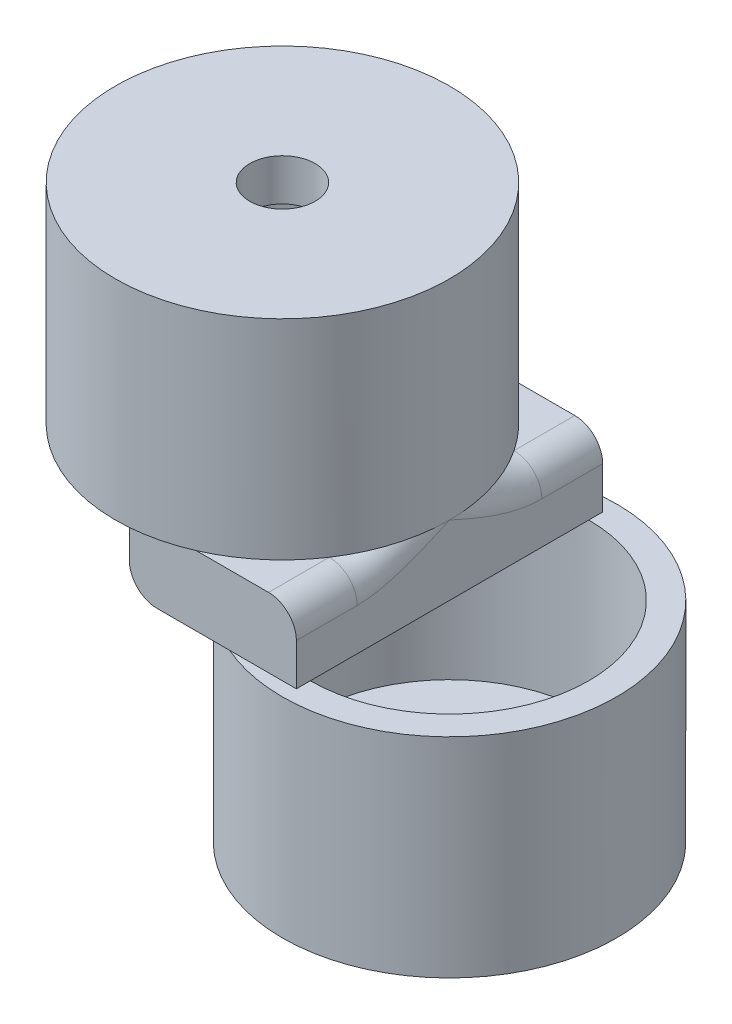
SolidWorks part; units mm, degrees
ref_plane "前视基准面" through (0, 0, 0) normal (0, 0, 1) x (1, 0, 0)
ref_plane "上视基准面" through (0, 0, 0) normal (0, 1, 0) x (1, 0, 0)
ref_plane "右视基准面" through (0, 0, 0) normal (1, 0, 0) x (0, 0, -1)
sketch "草图1" plane through (0, 0, 0) normal (0, 1, 0) x (1, 0, 0)
  circle A0 centre (0, 0) radius 12
  dimension "D1" = 24
extrude "凸台-拉伸1" add sketch "草图1" along normal blind 15
sketch "草图2" plane through (0, 0, 0) normal (0, 1, 0) x (1, 0, 0)
  circle A0 centre (12, 0) radius 12
  circle A1 centre (0, 0) radius 12 construction
  point P5 (9.8465, -1.7455)
  point P6 (9.7679, 2.1422)
  point P7 (9.9986, 0.17)
extrude "凸台-拉伸2" add sketch "草图2" against normal blind 15 from offset 5 offset against normal yes
sketch "草图3" plane through (0, 0, 0) normal (0, 1, 0) x (1, 0, 0)
  circle A2 centre (0, 0) radius 10
  circle A3 centre (0, 0) radius 10
  dimension "D1" = 2
extrude "切除-拉伸2" cut sketch "草图3" along normal blind 12
sketch "草图4" plane through (0, -5, 0) normal (0, 1, 0) x (1, 0, 0)
  circle A2 centre (12, 0) radius 10
  circle A3 centre (12, 0) radius 10
  dimension "D1" = 2
extrude "切除-拉伸3" cut sketch "草图4" against normal blind 12
sketch "草图7" plane through (0, 0, 0) normal (0, 0, 1) x (1, 0, 0)
  line L1 (12, 0) -> (0, 0)
  line L2 (12, 0) -> (12, -5)
  line L3 (12, -5) -> (0, -5)
  line L4 (0, 0) -> (0, -5)
extrude "凸台-拉伸3" add sketch "草图7" along normal mid plane 22
fillet "圆角1" radius 2 4 edges at (0, -5, -5.5) (12, 0, -5.5) (0, -5, 5.5) (12, 0, 5.5)
sketch "草图8" plane through (0, -20, 0) normal (0, -1, 0) x (1, 0, 0)
  line L0 (4.5, 0) -> (6.5, 0) construction
  line L1 (4.5, 1.505) -> (6.5, 1.505)
  line L2 (4.5, -1.505) -> (6.5, -1.505)
  line L3 (12, 7.5) -> (12, 5.5) construction
  line L4 (13.505, 7.5) -> (13.505, 5.5)
  line L5 (10.495, 7.5) -> (10.495, 5.5)
  line L6 (19.5, 0) -> (17.5, 0) construction
  line L7 (19.5, -1.505) -> (17.5, -1.505)
  line L8 (19.5, 1.505) -> (17.5, 1.505)
  line L9 (12, -7.5) -> (12, -5.5) construction
  line L10 (10.495, -7.5) -> (10.495, -5.5)
  line L11 (13.505, -7.5) -> (13.505, -5.5)
  circle A0 centre (12, 0) radius 1.85
  arc A2 (4.5, 1.505) -> (4.5, -1.505) centre (4.5, 0) ccw
  arc A3 (6.5, -1.505) -> (6.5, 1.505) centre (6.5, 0) ccw
  arc A4 (13.505, 7.5) -> (10.495, 7.5) centre (12, 7.5) ccw
  arc A5 (10.495, 5.5) -> (13.505, 5.5) centre (12, 5.5) ccw
  arc A6 (19.5, -1.505) -> (19.5, 1.505) centre (19.5, 0) ccw
  arc A7 (17.5, 1.505) -> (17.5, -1.505) centre (17.5, 0) ccw
  arc A8 (10.495, -7.5) -> (13.505, -7.5) centre (12, -7.5) ccw
  arc A9 (13.505, -5.5) -> (10.495, -5.5) centre (12, -5.5) ccw
  point P5 (5.5, 0)
  point P17 (12, 6.5)
  point P24 (18.5, 0)
  point P31 (12, -6.5)
  point P36 (12, 0)
  dimension "D1" = 3.7
  dimension "D2" = 1.505
  dimension "D3" = 2
  dimension "D4" = 6.5
  dimension "D5" = 4
extrude "切除-拉伸4" cut sketch "草图8" against normal blind 10
sketch "草图9" plane through (0, 15, 0) normal (0, 1, 0) x (1, 0, 0)
  circle A0 centre (0, 0) radius 2.35
  dimension "D1" = 4.7
extrude "切除-拉伸5" cut sketch "草图9" against normal blind 10
